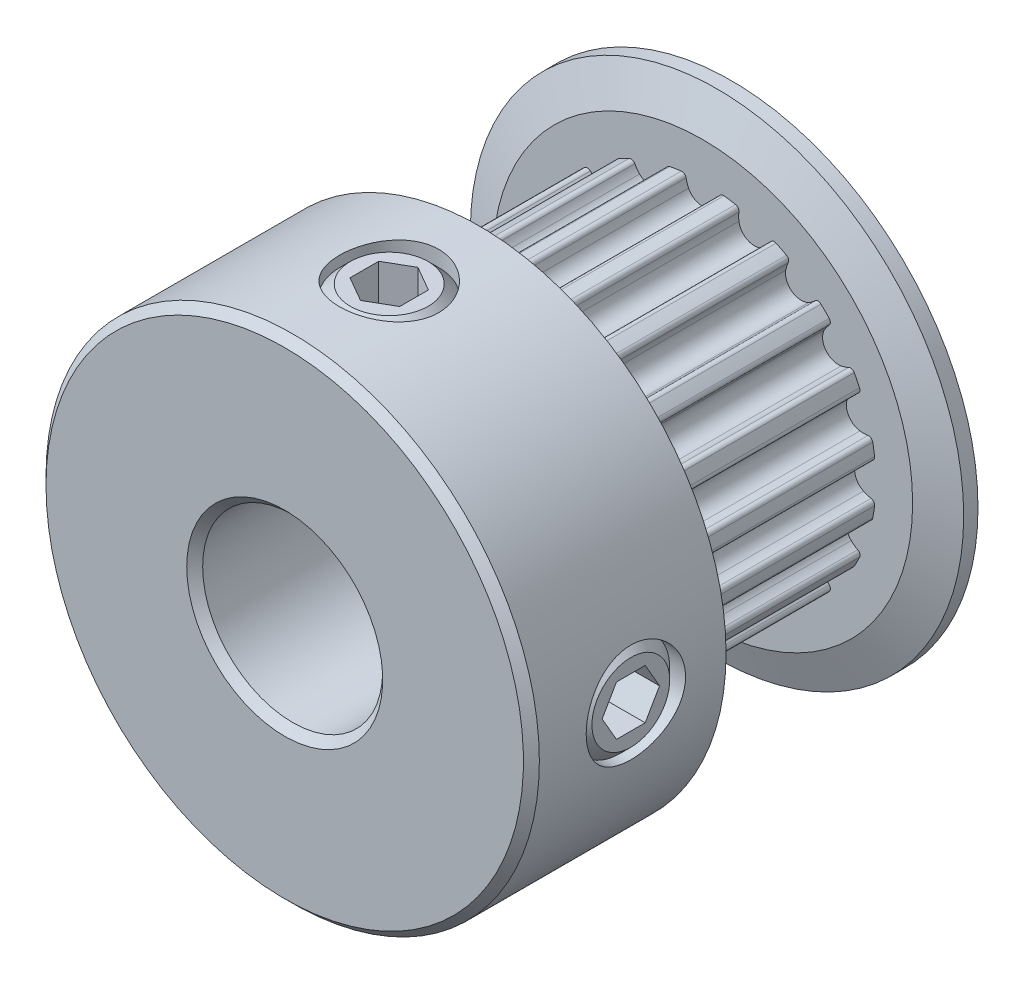
SolidWorks part; units mm, degrees
ref_plane "Front Plane" through (0, 0, 0) normal (0, 0, 1) x (1, 0, 0)
ref_plane "Top Plane" through (0, 0, 0) normal (0, 1, 0) x (1, 0, 0)
ref_plane "Right Plane" through (0, 0, 0) normal (1, 0, 0) x (0, 0, -1)
sketch "Sketch1" plane through (0, 0, 0) normal (0, 0, 1) x (1, 0, 0)
  line L1 (-1.7499, 5.3585) -> (1.7499, 5.3585) construction
  line L4 (0, 0) -> (0, 5.3585) construction
  line L5 (0, 5.3585) -> (0, 11.2107) construction
  line L6 (0, 6.3625) -> (1.9751, 6.0482) construction
  line L7 (1.9751, 6.0482) -> (2.6648, 5.8229) construction
  line L8 (1.9751, 6.0482) -> (1.7499, 5.3585) construction
  line L9 (-1.9751, 6.0482) -> (-1.7499, 5.3585) construction
  line L10 (-1.8963, 5.8067) -> (-2.841, 8.6995)
  line L11 (-2.841, 8.6995) -> (2.841, 8.6995)
  line L12 (2.841, 8.6995) -> (1.8963, 5.8067)
  circle A0 centre (0, 0) radius 6.3625 construction
  circle A1 centre (0, 0) radius 8.6995 construction
  circle A2 centre (0, 0) radius 6.1085 construction
  arc A3 (-0.4989, 5.6703) -> (0.4989, 5.6703) centre (0, 5.9135) ccw
  arc A4 (-0.4989, 5.6703) -> (-0.5855, 5.9387) centre (0.4, 6.1085) cw
  arc A5 (-1.8963, 5.8067) -> (-0.7518, 6.0621) centre (0, 0) cw
  arc A6 (-0.5855, 5.9387) -> (-0.7518, 6.0621) centre (-0.7333, 5.9132) ccw
  arc A7 (1.8963, 5.8067) -> (0.7518, 6.0621) centre (0, 0) ccw
  arc A8 (0.5855, 5.9387) -> (0.7518, 6.0621) centre (0.7333, 5.9132) cw
  arc A9 (0.4989, 5.6703) -> (0.5855, 5.9387) centre (-0.4, 6.1085) ccw
  point P6 (0, 20.9083)
  point P11 (0, 6.3625)
  point P13 (0, 8.6995)
  point P14 (0, 6.1085)
  dimension "D1" = 9.6976
  dimension "D2" = 4.8482
sketch "Sketch2" plane through (0, 0, 0) normal (1, 0, 0) x (0, 0, -1)
  line L0 (-7.875, 3.175) -> (7.875, 3.175)
  line L1 (-7.875, 3.175) -> (-7.875, 8.6995)
  line L2 (-1.01, 8.6995) -> (-7.875, 8.6995)
  line L3 (-1.515, 3.175) -> (-1.515, 8.6995) construction
  line L4 (-1.515, 8.6995) -> (-0.505, 8.6995) construction
  line L5 (-0.505, 8.6995) -> (-0.505, 6.1085) construction
  line L6 (-0.505, 6.1085) -> (6.865, 6.1085)
  line L7 (6.865, 6.1085) -> (6.865, 8.6995) construction
  line L8 (6.865, 8.6995) -> (7.875, 8.6995) construction
  line L9 (7.875, 8.6995) -> (7.875, 3.175)
  line L10 (-7.875, 0) -> (7.875, 0) construction
  line L11 (7.37, 8.6995) -> (6.865, 7.404)
  line L12 (-0.505, 7.404) -> (-1.01, 8.6995)
  line L14 (-0.505, 7.404) -> (-0.505, 6.1085)
  line L15 (6.865, 6.1085) -> (6.865, 7.404)
  line L16 (7.37, 8.6995) -> (7.875, 8.6995)
  arc A0 (-0.505, 7.404) -> (-1.01, 8.6995) centre (-2.4192, 7.404) ccw construction
  arc A1 (6.865, 7.404) -> (7.37, 8.6995) centre (8.7792, 7.404) cw construction
  point P12 (-0.505, 7.404)
  point P14 (-1.01, 8.6995)
  point P20 (6.865, 7.404)
  point P21 (7.37, 8.6995)
  point P25 (6.865, 0)
  point P26 (-0.505, 0)
  dimension "OA" = 15.75
  dimension "Bore" = 6.35
  dimension "Outside Width" = 8.38
  dimension "Inside Width" = 7.37
revolve "Revolve1" add sketch "Sketch2" angle 360 mid plane about L10
sketch "Sketch3" plane through (0, 0, 0) normal (0, 0, 1) x (1, 0, 0)
  line L6 (2.841, 8.6995) -> (-2.841, 8.6995)
  line L7 (1.8963, 5.8067) -> (2.841, 8.6995)
  line L8 (-2.841, 8.6995) -> (-1.8963, 5.8067)
  line L9 (2.841, 8.6995) -> (-2.841, 8.6995)
  line L10 (1.8963, 5.8067) -> (2.841, 8.6995)
  line L11 (-2.841, 8.6995) -> (-1.8963, 5.8067)
  arc A8 (1.8963, 5.8067) -> (0.7518, 6.0621) centre (0, 0) ccw
  arc A9 (0.7518, 6.0621) -> (0.5855, 5.9387) centre (0.7333, 5.9132) ccw
  arc A10 (0.4989, 5.6703) -> (0.5855, 5.9387) centre (-0.4, 6.1085) ccw
  arc A11 (-0.4989, 5.6703) -> (0.4989, 5.6703) centre (0, 5.9135) ccw
  arc A12 (-0.5855, 5.9387) -> (-0.4989, 5.6703) centre (0.4, 6.1085) ccw
  arc A13 (-0.5855, 5.9387) -> (-0.7518, 6.0621) centre (-0.7333, 5.9132) ccw
  arc A14 (-0.7518, 6.0621) -> (-1.8963, 5.8067) centre (0, 0) ccw
  arc A15 (1.8963, 5.8067) -> (0.7518, 6.0621) centre (0, 0) ccw
  arc A16 (0.7518, 6.0621) -> (0.5855, 5.9387) centre (0.7333, 5.9132) ccw
  arc A17 (0.4989, 5.6703) -> (0.5855, 5.9387) centre (-0.4, 6.1085) ccw
  arc A18 (-0.4989, 5.6703) -> (0.4989, 5.6703) centre (0, 5.9135) ccw
  arc A19 (-0.5855, 5.9387) -> (-0.4989, 5.6703) centre (0.4, 6.1085) ccw
  arc A20 (-0.5855, 5.9387) -> (-0.7518, 6.0621) centre (-0.7333, 5.9132) ccw
  arc A21 (-0.7518, 6.0621) -> (-1.8963, 5.8067) centre (0, 0) ccw
  dimension "D1" = 0
extrude "Cut-Extrude1" cut sketch "Sketch3" against normal up to vertex (6.865 mm away) from vertex up to point (0, 6.1085, -6.865) starting at point (0, 6.1085, 0.505)
pattern_circular "CirPattern1" count 20 over 360 about axis through (0, 0, 7.875) along (0, 0, 1) of "Cut-Extrude1"
sketch "Sketch4" plane through (0, 0, 0) normal (1, 0, 0) x (0, -1, 0)
  line L0 (0, -0.505) -> (0, -7.875) construction
  line L1 (-3.175, -7.875) -> (3.175, -7.875) construction
  line L2 (7.404, -0.505) -> (-7.404, -0.505) construction
  circle A0 centre (0, -4.19) radius 1.7526
extrude "Cut-Extrude2" cut sketch "Sketch4" along normal through all
ref_plane "Plane1" through (0, 0, 4.19) normal (0, 0, 1) x (1, 0, 0)
sketch "Sketch5" plane through (0, 0, 4.19) normal (0, 0, 1) x (1, 0, 0)
  line L0 (0, 0) -> (0, 8.6995) construction
  line L1 (3.175, -1.3716) -> (3.175, 0)
  line L2 (3.556, -1.7526) -> (8.1401, -1.7526)
  line L3 (3.175, 0) -> (8.6995, 0) construction
  line L4 (3.175, 0) -> (8.5211, 0)
  line L5 (8.5211, 0) -> (8.5211, -1.3716)
  line L6 (3.556, -1.7526) -> (3.175, -1.3716)
  line L7 (8.5211, -1.3716) -> (8.1401, -1.7526)
  circle A0 centre (0, 0) radius 8.6995 construction
  circle A1 centre (0, 0) radius 3.175 construction
  point P2 (3.175, -1.7526)
  point P11 (8.5211, -1.7526)
revolve "Revolve2" add sketch "Sketch5" angle 360 mid plane about L4
sketch "Sketch6" plane through (8.5211, 5.3841, 0) normal (-1, 0, 0) x (0, -1, 0)
  line L1 (5.3841, 5.2019) -> (4.5078, 4.6959)
  line L2 (4.5078, 4.6959) -> (4.5078, 3.6841)
  line L3 (4.5078, 3.6841) -> (5.3841, 3.1781)
  line L4 (5.3841, 3.1781) -> (6.2604, 3.6841)
  line L5 (6.2604, 3.6841) -> (6.2604, 4.6959)
  line L6 (6.2604, 4.6959) -> (5.3841, 5.2019)
  circle A0 centre (5.3841, 4.19) radius 0.8763 construction
  dimension "D1" = 1.7526
extrude "Cut-Extrude3" cut sketch "Sketch6" along normal blind 1.3144
pattern_circular "CirPattern3" count 2 over 90 about axis through (0, 0, 7.875) along (0, 0, 1) of "Cut-Extrude2", "Revolve2", "Cut-Extrude3"
chamfer "Chamfer1" distance 0.2807 angle 45 2 edges at (3.175, 0, 7.875) (8.6995, 0, 7.875)
ref_axis "Center Axis 1" through (0, 0, -7.875) along (0, 0, 1)
ref_plane "Contact Plane 1" through (0, 0, 7.875) normal (0, 0, 1) x (1, 0, 0)
ref_plane "Contact Plane 2" through (0, 0, -7.875) normal (0, 0, -1) x (-1, 0, 0)
equation "\"D2@Sketch1\"= \"D1@Sketch1\" / 2"
equation "\"D1@Sketch6\" = \"Set Screw@Sketch4\" / 2"
equation "\"D1@Cut-Extrude3\" = \"D1@Sketch6\"*.75"
